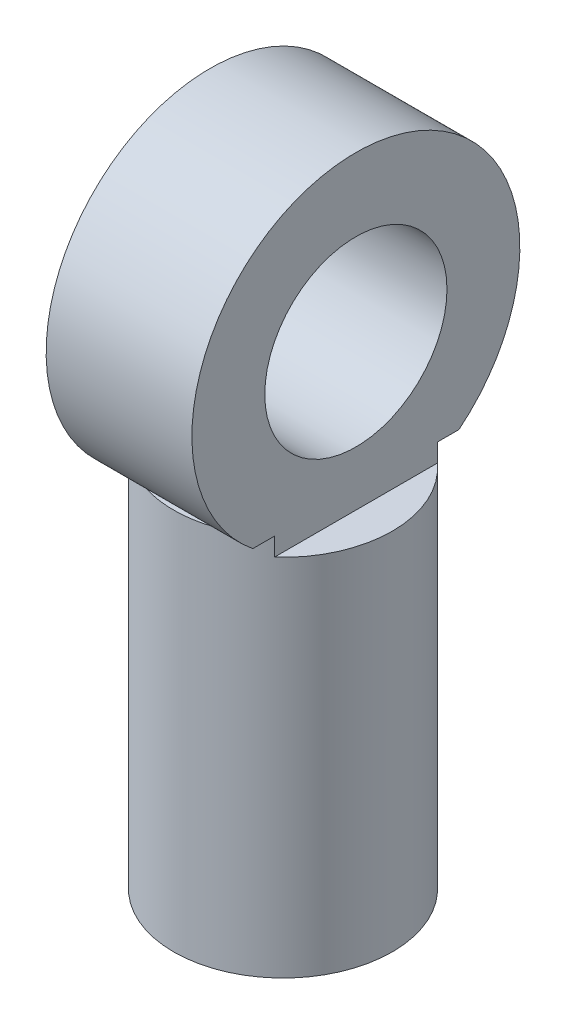
SolidWorks part; units mm, degrees
ref_plane "Front Plane" through (0, 0, 0) normal (0, 0, 1) x (1, 0, 0)
ref_plane "Top Plane" through (0, 0, 0) normal (0, 1, 0) x (1, 0, 0)
ref_plane "Right Plane" through (0, 0, 0) normal (1, 0, 0) x (0, 0, -1)
sketch "Sketch1" plane through (0, 0, 0) normal (0, 1, 0) x (1, 0, 0)
  circle A0 centre (0, 0) radius 3
  dimension "D1" = 6
extrude "Boss-Extrude1" add sketch "Sketch1" along normal blind 10
sketch "Sketch2" plane through (0, 0, 0) normal (0, -1, 0) x (1, 0, 0)
  circle A0 centre (0, 0) radius 1.55
  dimension "D1" = 3.1
extrude "Cut-Extrude1" cut sketch "Sketch2" against normal blind 9
sketch "Sketch3" plane through (0, 0, 0) normal (1, 0, 0) x (0, 0, -1)
  line L0 (3, 10) -> (-3, 10) construction
  line L1 (-3, 10) -> (-3, 0) construction
  line L2 (-3, 10) -> (3, 10)
  line L3 (-3, 10) -> (-3, 10.5)
  line L4 (-3, 10.5) -> (3, 10.5)
  line L5 (3, 10) -> (3, 10.5)
  line L6 (3, 0) -> (3, 10) construction
  circle A0 centre (0, 14) radius 4.5
  dimension "D1" = 9
  dimension "D2" = 4
  dimension "D3" = 0.5
  dimension "D4" = 0
  dimension "D5" = 0
extrude "Boss-Extrude2" add sketch "Sketch3" along normal blind 2 and the other way blind 2 contours A0 L3 L2 | L3 A0 L5 L4 | L5 A0 L3 L4 | L5 L4 L3 L2 region at (0, 10.1897, 2.6907) region at (0, 10.2628, 0) region at (0, 14.2525, 0)
sketch "Sketch4" plane through (2, 0, 0) normal (1, 0, 0) x (0, 0, -1)
  circle A0 centre (0, 14) radius 2.5
  dimension "D1" = 5
extrude "Cut-Extrude2" cut sketch "Sketch4" against normal through all
extrude "Cut-Extrude3" cut sketch "Sketch1<2>" along normal blind 10.5 flip side to cut
sketch "Sketch1<2>" plane through (0, 0, 0) normal (0, 1, 0) x (1, 0, 0) same geometry as "Sketch1"
